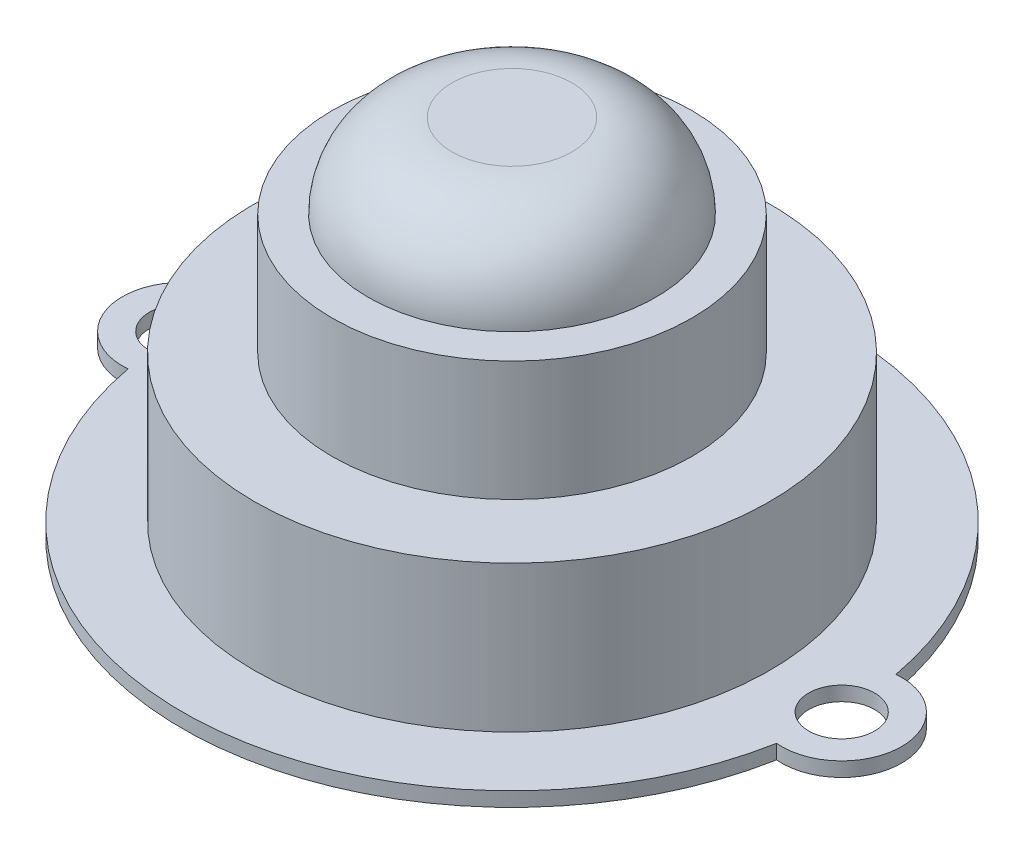
SolidWorks part; units mm, degrees
ref_plane "Front Plane" through (0, 0, 0) normal (0, 0, 1) x (1, 0, 0)
ref_plane "Top Plane" through (0, 0, 0) normal (0, 1, 0) x (1, 0, 0)
ref_plane "Right Plane" through (0, 0, 0) normal (1, 0, 0) x (0, 0, -1)
sketch "Sketch1" plane through (0, 0, 0) normal (0, 1, 0) x (1, 0, 0)
  arc A0 (-27.0455, -4.9793) -> (27.0455, -4.9793) centre (0, 0) ccw
  arc A1 (-27.0455, 4.9793) -> (-27.0455, -4.9793) centre (-27.5, 0) ccw
  arc A2 (27.0455, -4.9793) -> (27.0455, 4.9793) centre (27.5, 0) ccw
  arc A3 (27.0455, 4.9793) -> (-27.0455, 4.9793) centre (0, 0) ccw
  circle A4 centre (-27.5, 0) radius 2.75
  circle A5 centre (27.5, 0) radius 2.75
  dimension "D1" = 55
  dimension "D2" = 10
  dimension "D3" = 5.5
extrude "Boss-Extrude1" add sketch "Sketch1" along normal blind 1.2
sketch "Sketch2" plane through (0, 1.2, 0) normal (0, 1, 0) x (1, 0, 0)
  circle A0 centre (0, 0) radius 21.5
extrude "Boss-Extrude2" add sketch "Sketch2" along normal blind 12.2
sketch "Sketch3" plane through (0, 13.4, 0) normal (0, 1, 0) x (1, 0, 0)
  circle A0 centre (0, 0) radius 15
  dimension "D1" = 30
extrude "Boss-Extrude3" add sketch "Sketch3" along normal blind 10
sketch "Sketch5" plane through (0, 23.4, 0) normal (0, 1, 0) x (1, 0, 0)
  circle A0 centre (0, 0) radius 12
extrude "Boss-Extrude4" add sketch "Sketch5" along normal blind 7
fillet "Fillet1" radius 7 1 edges at (0, 30.4, 12)
